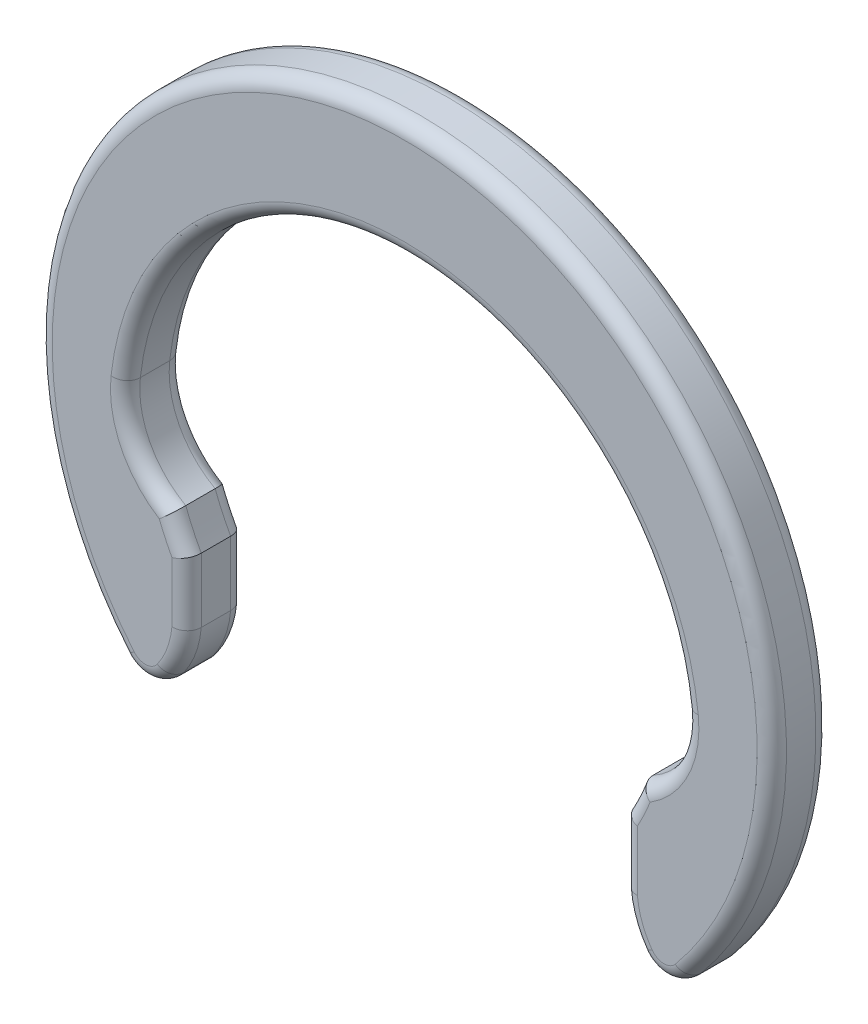
SolidWorks part; units mm, degrees
ref_plane "Front" through (0, 0, 0) normal (0, 0, 1) x (1, 0, 0)
ref_plane "Top" through (0, 0, 0) normal (0, 1, 0) x (1, 0, 0)
ref_plane "Right" through (0, 0, 0) normal (1, 0, 0) x (0, 0, -1)
sketch "Sketch1" plane through (0, 0, 0) normal (0, 0, 1) x (1, 0, 0)
  line L0 (0, 5) -> (0, -5) construction
  line L1 (-3.4, 0) -> (-5, 0) construction
  line L2 (-4.2, 0) -> (-3.4, 0) construction
  line L3 (-3.4, 0) -> (3.4, 0) construction
  line L4 (-2.9698, -2.9698) -> (-2.9698, -1.6553) construction
  line L5 (-3.1812, -1.2) -> (3.1812, -1.2) construction
  line L6 (-3.4, 0) -> (-3.4, -1.2) construction
  line L7 (0, 0) -> (-2.4042, -2.4042) construction
  line L8 (-2.4042, -2.4042) -> (-3.5355, -3.5355) construction
  circle A0 centre (0, 0) radius 5 construction
  circle A1 centre (0, 0) radius 3.4 construction
  arc A2 (0, 3.4) -> (-3.8, 0) centre (0, -0.4235) ccw construction
  arc A5 (-3.1812, -1.2) -> (-3.8, 0) centre (-2.5888, -0.135) cw construction
  point P21 (0, 3.4)
  point P23 (0, 5)
  dimension "Ring OD" = 10
  dimension "D3" = 6.8
  dimension "Max Section" = 1.6
  dimension "D1" = 45
  dimension "D2" = 1.2
  dimension "D4" = 1.2
sketch "Sketch3" plane through (0, 0, 0) normal (0, 1, 0) x (1, 0, 0)
  line L0 (-5, 0.4) -> (-5, -0.4) construction
  line L3 (-3.4, 0) -> (-5, 0) construction
  point P3 (-5, 0)
  dimension "Ring Thickness" = 0.8
sketch "Sketch2" plane through (0, 0, 0) normal (0, 0, 1) x (1, 0, 0)
  line L0 (-2.9698, -2.9698) -> (-2.9698, -2.5317) construction
  line L1 (-2.9698, -2.5317) -> (-2.9698, -2.0935)
  line L2 (-2.9698, -2.0935) -> (-2.9698, -1.6553)
  line L3 (0, 3.4) -> (0, 0) construction
  line L4 (0, 5) -> (0, -5) construction
  line L5 (-2.9698, -2.9698) -> (-3.1584, -3.1584) construction
  line L6 (0, 5) -> (0, 3.4) construction
  line L7 (-3.1584, -3.1584) -> (-3.347, -3.347) construction
  line L8 (-3.347, -3.347) -> (-3.5355, -3.5355)
  line L9 (-2.4042, -2.4042) -> (-3.5355, -3.5355) construction
  line L10 (2.9698, -2.0935) -> (2.9698, -1.6553)
  line L11 (2.9698, -2.5317) -> (2.9698, -2.0935)
  line L12 (3.347, -3.347) -> (3.5355, -3.5355)
  circle A0 centre (0, 0) radius 5 construction
  arc A1 (0, 3.4) -> (-3.8, 0) centre (0, -0.4235) ccw construction
  circle A3 centre (0, 0) radius 3.4 construction
  arc A4 (3.5355, -3.5355) -> (-3.5355, -3.5355) centre (0, 0) ccw
  arc A5 (3.8, 0) -> (-3.8, 0) centre (0, -0.4235) ccw
  arc A6 (-3.8, 0) -> (-3.1812, -1.2) centre (-2.5888, -0.135) ccw construction
  arc A7 (-3.1812, -1.2) -> (-2.9698, -1.6553) centre (0, 0) ccw
  arc A8 (-2.9698, -2.5317) -> (-3.347, -3.347) centre (-4.2678, -2.4262) cw
  arc A9 (2.9698, -2.5317) -> (3.347, -3.347) centre (4.2678, -2.4262) ccw
  arc A10 (3.1812, -1.2) -> (2.9698, -1.6553) centre (0, 0) cw
  arc A11 (3.8, 0) -> (3.1812, -1.2) centre (2.5888, -0.135) cw
  arc A12 (-3.8, 0) -> (-3.1812, -1.2) centre (-2.5888, -0.135) ccw
extrude "Boss-Extrude1" add sketch "Sketch2" along normal mid plane 0.8
fillet "Fillet1" radius 0.4 2 edges at (3.5355, -3.5355, 0) (-3.5355, -3.5355, 0)
fillet "Fillet2" radius 0.2 24 edges at (-3.5157, -3.3473, -0.4) (-3.0439, -2.8711, -0.4) (-2.9698, -2.0935, -0.4) (-3.0839, -1.4316, -0.4) (-3.672, -0.6935, -0.4) (0, 3.4, -0.4) (3.672, -0.6935, -0.4) (3.0839, -1.4316, -0.4) (2.9698, -2.0935, -0.4) (3.0439, -2.8711, -0.4) (3.5157, -3.3473, -0.4) (0, 5, -0.4) (2.9698, -2.0935, 0.4) (3.0839, -1.4316, 0.4) (3.672, -0.6935, 0.4) (0, 3.4, 0.4) (-3.672, -0.6935, 0.4) (-3.0839, -1.4316, 0.4) (-2.9698, -2.0935, 0.4) (-3.0439, -2.8711, 0.4) (-3.5157, -3.3473, 0.4) (0, 5, 0.4) (3.5157, -3.3473, 0.4) (3.0439, -2.8711, 0.4)
ref_axis "Center Axis 1" through (0, 0, 0.2) along (0, 0, -1)
ref_plane "Contact Plane 1" through (0, 0, 0.4) normal (0, 0, 1) x (1, 0, 0)
ref_plane "Contact Plane 2" through (0, 0, -0.4) normal (0, 0, -1) x (-1, 0, 0)
equation "\"D1@Boss-Extrude1\"=\"Ring Thickness@Sketch3\""
equation "\"D1@Fillet1\" = \"Max Section@Sketch1\" / 4"
equation "\"D2@Sketch1\"=\"Max Section@Sketch1\"*.75"
equation "\"D4@Sketch1\"=\"Max Section@Sketch1\"*.75"
equation "\"D1@Fillet2\"=\"Ring Thickness@Sketch3\"/4"
